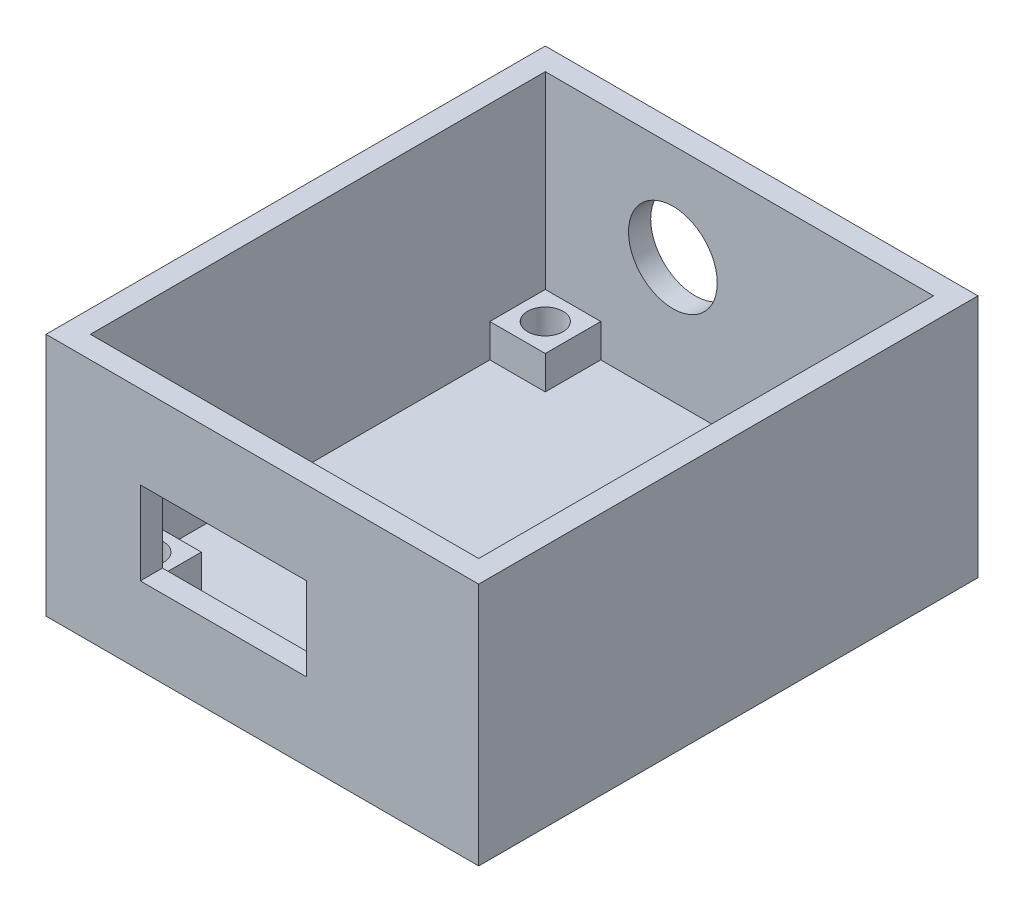
SolidWorks part; units mm, degrees
ref_plane "Front Plane" through (0, 0, 0) normal (0, 0, 1) x (1, 0, 0)
ref_plane "Top Plane" through (0, 0, 0) normal (0, 1, 0) x (1, 0, 0)
ref_plane "Right Plane" through (0, 0, 0) normal (1, 0, 0) x (0, 0, -1)
sketch "Sketch1" plane through (0, 0, 0) normal (0, 1, 0) x (1, 0, 0)
  line L1 (19.5, -22.5) -> (-19.5, -22.5)
  line L2 (19.5, -22.5) -> (19.5, 22.5)
  line L3 (19.5, 22.5) -> (-19.5, 22.5)
  line L4 (-19.5, -22.5) -> (-19.5, 22.5)
  line L5 (19.5, -22.5) -> (-19.5, 22.5) construction
  line L6 (19.5, 22.5) -> (-19.5, -22.5) construction
  point P0 (0, 0)
  dimension "D1" = 45
  dimension "D2" = 39
extrude "Body" add sketch "Sketch1" along normal blind 22
shell "Shell1" thickness 2 removed face at (0, 22, 0)
sketch "Sketch3" plane through (0, 2, 0) normal (0, 1, 0) x (1, 0, 0)
  line L0 (-1000, 0) -> (49000, 0) construction
  line L5 (-17.5, 20.5) -> (-12.5, 20.5)
  line L6 (-17.5, 20.5) -> (-17.5, 15.5)
  line L7 (-17.5, 15.5) -> (-12.5, 15.5)
  line L8 (-12.5, 20.5) -> (-12.5, 15.5)
  line L9 (0, -1000) -> (0, 49000) construction
  line L10 (12.5, 20.5) -> (12.5, 15.5)
  line L11 (17.5, 15.5) -> (12.5, 15.5)
  line L12 (17.5, 20.5) -> (17.5, 15.5)
  line L13 (17.5, 20.5) -> (12.5, 20.5)
  line L14 (17.5, -20.5) -> (12.5, -20.5)
  line L15 (17.5, -20.5) -> (17.5, -15.5)
  line L16 (17.5, -15.5) -> (12.5, -15.5)
  line L17 (12.5, -20.5) -> (12.5, -15.5)
  line L18 (-12.5, -20.5) -> (-12.5, -15.5)
  line L19 (-17.5, -15.5) -> (-12.5, -15.5)
  line L20 (-17.5, -20.5) -> (-17.5, -15.5)
  line L21 (-17.5, -20.5) -> (-12.5, -20.5)
  dimension "D1" = 5
extrude "Inserts_Support" add sketch "Sketch3" along normal blind 3
sketch "Sketch4" plane through (0, 5, 0) normal (0, 1, 0) x (1, 0, 0)
  line L1 (15, -18) -> (-15, -18) construction
  line L2 (15, -18) -> (15, 18) construction
  line L3 (15, 18) -> (-15, 18) construction
  line L4 (-15, -18) -> (-15, 18) construction
  line L5 (15, -18) -> (-15, 18) construction
  line L6 (15, 18) -> (-15, -18) construction
  circle A0 centre (-15, 18) radius 1.6
  circle A1 centre (15, 18) radius 1.6
  circle A2 centre (15, -18) radius 1.6
  circle A3 centre (-15, -18) radius 1.6
  point P0 (0, 0)
  dimension "D3" = 3.2
  dimension "D1" = 30
  dimension "D2" = 36
extrude "Inserts_Holes" cut sketch "Sketch4" against normal blind 4
sketch "Sketch5" plane through (0, 0, 22.5) normal (0, 0, 1) x (1, 0, 0)
  line L0 (-19.5, 22) -> (-19.5, 0) construction
  line L1 (-11, 14.5) -> (4, 14.5)
  line L2 (-11, 14.5) -> (-11, 7)
  line L3 (-11, 7) -> (4, 7)
  line L4 (4, 14.5) -> (4, 7)
  line L5 (-11, 14.5) -> (4, 7) construction
  line L6 (-11, 7) -> (4, 14.5) construction
  point P0 (-3.5, 10.75)
  point P5 (-2.2085, 11.0736)
  dimension "D1" = 7.5
  dimension "15" = 15
  dimension "D2" = 8.5
  dimension "D3" = 7
extrude "USB_Hole" cut sketch "Sketch5" against normal up to next
sketch "Sketch6" plane through (0, 0, -22.5) normal (0, 0, -1) x (-1, 0, 0)
  line L0 (19.5, 22) -> (19.5, 0) construction
  circle A0 centre (6, 13.25) radius 4
  dimension "D1" = 8
  dimension "D2" = 13.25
  dimension "D3" = 13.5
extrude "Jack_Hole" cut sketch "Sketch6" against normal up to next
